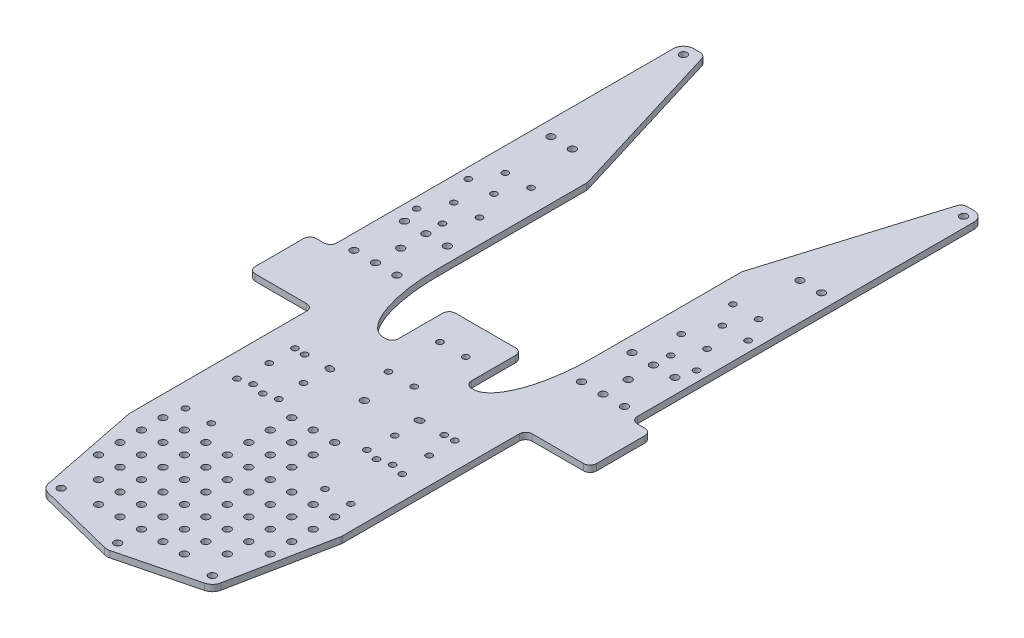
SolidWorks part; units mm, degrees
material "Acrylic (Medium-high impact)"
ref_plane "Front" through (0, 0, 0) normal (0, 0, 1) x (1, 0, 0)
ref_plane "Top" through (0, 0, 0) normal (0, 1, 0) x (1, 0, 0)
ref_plane "Right" through (0, 0, 0) normal (1, 0, 0) x (0, 0, -1)
sketch "Top Layout" plane through (0, 0, 0) normal (0, 1, 0) x (1, 0, 0)
  line L0 (45.5, 0) -> (0, 0) construction
  line L6 (15.5, -88.75) -> (58.5, -88.75) construction
  line L25 (45.5, 0) -> (88.5, 0) construction
  line L26 (88.5, 70) -> (88.5, -70) construction
  line L27 (58.5, -18.75) -> (58.5, -158.75) construction
  line L31 (36, 88.75) -> (79, 88.75) construction
  line L32 (79, 158.75) -> (79, 18.75) construction
  point P0 (0, 0)
  point P6 (0, 0)
  point P8 (53, -32.3497)
  line B0 (70, 100) -> (36, 100) construction
  line B1 (70, 100) -> (70, 53.5) construction
  line B2 (70, 53.5) -> (36, 53.5) construction
  line B3 (36, 100) -> (36, 53.5) construction
  line B4 (53, 100) -> (53, 88.75) construction
  line B5 (-6, -22.6978) -> (-6, 1.3022) construction
  line B6 (-17, -29.9478) -> (-17, 16.5522) construction
  line B7 (-17, -29.9478) -> (17, -29.9478) construction
  line B8 (17, -29.9478) -> (17, 16.5522) construction
  line B9 (-17, 16.5522) -> (17, 16.5522) construction
  line B10 (-6, 1.3022) -> (6, 1.3022) construction
  line B11 (6, 1.3022) -> (6, -22.6978) construction
  line B12 (6, -22.6978) -> (-6, -22.6978) construction
  line B13 (0, -22.6978) -> (0, -29.9478) construction
  line B14 (17, 5.3022) -> (-19, 5.3022) construction
  line B15 (49.5, -53.5) -> (15.5, -53.5) construction
  line B16 (49.5, -53.5) -> (49.5, -100) construction
  line B17 (49.5, -100) -> (15.5, -100) construction
  line B18 (15.5, -53.5) -> (15.5, -100) construction
  line B19 (32.5, -88.75) -> (32.5, -100) construction
  line B20 (45.5, 14.25) -> (79.5, 14.25) construction
  line B21 (45.5, 14.25) -> (45.5, -14.25) construction
  line B22 (45.5, -14.25) -> (79.5, -14.25) construction
  line B23 (79.5, 14.25) -> (79.5, -14.25) construction
  dimension "D1" = 30
  dimension "D2" = 70
  dimension "D3" = 9.5
  dimension "D4" = 4.5
  dimension "D5" = 100
  dimension "D7" = 9
  dimension "D8" = 140
  dimension "D9" = 100
sketch_block_instance "Flat 430 Block-1"
sketch_block "Flat 430 Block" parameters "D1"=46.5, "D2"=34, "D3"=11.25, "D4"=6.2771, "D5"=20.8671, "D6"=8.1058, "D7"=13.2568
sketch_block_instance "DYNAMIXEL 430 Side-1"
sketch_block "DYNAMIXEL 430 Side" parameters "D1"=34, "D2"=46.5, "D3"=12, "D4"=24, "D5"=11.25, "D6"=2, "D7"=4
sketch_block_instance "Block2-1"
sketch_block "Block2" parameters "D1"=12, "D2"=11, "D3"=4, "D4"=24, "D5"=13.103, "D6"=44.647, "D7"=34
sketch_block_instance "DYNAMIXEL 430 TopBot-1"
sketch_block "DYNAMIXEL 430 TopBot" parameters "D1"=28.5, "D2"=34, "D3"=20.267, "D4"=13.9544, "D5"=12.6443, "D6"=6.0635
sketch "Sketch4" plane through (0, 0, 0) normal (1, 0, 0) x (0, 0, -1)
  line L1 (-100, 0) -> (100, 0)
  line L5 (100, -3) -> (-100, -3)
  line L8 (100, -3) -> (100, 0)
  line L9 (-100, -3) -> (-100, 0)
  line L10 (158.75, 0) -> (18.75, 0) construction
  line B0 (-100, 14.25) -> (-88.75, 14.25) construction
  line B1 (-53.5, 0) -> (-100, 0) construction
  line B2 (-53.5, 0) -> (-53.5, 28.5) construction
  line B3 (-53.5, 28.5) -> (-100, 28.5) construction
  line B4 (-100, 0) -> (-100, 28.5) construction
  line B5 (100, 14.25) -> (88.75, 14.25) construction
  line B6 (53.5, 28.5) -> (100, 28.5) construction
  line B7 (53.5, 28.5) -> (53.5, 0) construction
  line B8 (53.5, 0) -> (100, 0) construction
  line B9 (100, 28.5) -> (100, 0) construction
  dimension "D2" = 3
sketch_block_instance "DYNAMIXEL 430 Front-1"
sketch_block "DYNAMIXEL 430 Front" parameters "D1"=46.5, "D2"=28.5, "D3"=11.25, "D4"=8, "D5"=8, "D6"=11, "D7"=11
sketch_block_instance "DYNAMIXEL 430 Front-3"
extrude "Boss-Extrude1" add sketch "Sketch4" along normal up to vertex (79.5 mm away)
ref_plane "Plane1" through (45.5, 0, 0) normal (1, 0, 0) x (0, 0, -1)
hole_wizard "M2.5 Clearance Hole2" positions "Sketch12" profile "Sketch13" hole size "M2.5" standard "ANSI Metric" end condition through all
sketch "Sketch12" plane through (0, -3, 0) normal (0, 1, 0) x (1, 0, 0)
  point P0 (26.5, -84.75)
  point P3 (38.5, -84.75)
  point P6 (38.5, -60.75)
  point P9 (26.5, -60.75)
  point P18 (59, 84.75)
  point P21 (47, 84.75)
  point P24 (47, 60.75)
  point P27 (59, 60.75)
  point P30 (6, -22.6978)
  point P32 (6, 1.3022)
  point P38 (65.2, 73.65)
  point P41 (53.2, 73.65)
  point P44 (53.2, 49.65)
  point P47 (65.2, 49.65)
sketch "Sketch13" plane through (26.5, -3, 84.75) normal (1, 0, 0) x (0, 0, -1)
  line L0 (0, 0) -> (0, 3)
  line L1 (0, 3) -> (1.45, 3)
  line L2 (1.45, 3) -> (1.45, 0)
  line L5 (1.45, 0) -> (0, 0)
  line L11 (0, -6.35) -> (0, 107.95) construction
  dimension "Thru Hole Dia." = 2.9
  dimension "Thru Hole Depth" = 3
sketch "Sketch14" plane through (0, 0, 0) normal (0, 1, 0) x (1, 0, 0)
  line L1 (79.5, 100) -> (70, 100)
  line L2 (79.5, 100) -> (79.5, 14.25)
  line L3 (79.5, 14.25) -> (70, 14.25)
  line L4 (70, 100) -> (70, 14.25)
  line L5 (45.5, -14.25) -> (79.5, -14.25) construction
  line L6 (79.5, -100) -> (49.5, -100)
  line L7 (79.5, -100) -> (79.5, -14.25)
  line L8 (79.5, -14.25) -> (49.5, -14.25)
  line L9 (49.5, -100) -> (49.5, -14.25)
  line L10 (17, 16.5522) -> (17, -10)
  line L11 (0, 100) -> (36, 100)
  line L12 (0, 100) -> (0, 16.5522)
  line L13 (0, 16.5522) -> (17, 16.5522)
  line L15 (17, -29.9478) -> (17, 16.5522) construction
  line L16 (17, -10) -> (36, -10)
  line L17 (36, -10) -> (36, 100)
  line L18 (79.5, 100) -> (0, 100) construction
  line L21 (36, 100) -> (36, 53.5) construction
  line L22 (45.5, 14.25) -> (79.5, 14.25) construction
  point P4 (49.5, -14.25)
  point P5 (70, 14.25)
  point P26 (0, 0)
  point P30 (0, 0)
  dimension "D2" = 110
extrude "Cut-Extrude1" cut sketch "Sketch14" against normal through all
fillet "Fillet3" radius 15 1 edges at (36, -1.5, 10)
mirror "Mirror1" about plane through (0, 0, 0) normal (1, 0, 0) of bodies 121
sketch "Sketch18" plane through (0, 0, 0) normal (0, 1, 0) x (1, 0, 0)
  line L0 (0, -50) -> (0, 50) construction
  line L2 (36.4427, -150.774) -> (1.2271, -159.6893)
  line L3 (-1.2271, -159.6893) -> (-36.4427, -150.774)
  line L4 (49.5, -100) -> (-49.5, -100) construction
  line L5 (49.5, -100) -> (40.1185, -146.9075)
  line L6 (-49.5, -100) -> (-40.1185, -146.9075)
  line L7 (49.5, -100) -> (-49.5, -100)
  line L8 (49.5, -100) -> (49.5, -135.5765) construction
  line L9 (-49.5, -100) -> (-49.5, -135.5765) construction
  line L10 (45.5, 0) -> (0, 0) construction
  line L11 (36, 30) -> (36, 100) construction
  line L12 (70, 100) -> (36, 100)
  line L13 (70, 100) -> (70, 173.9875)
  line L16 (70, 100) -> (36, 100) construction
  line L19 (-70, 100) -> (-70, 173.9875)
  line L20 (-70, 100) -> (-36, 100)
  line L21 (36, 100) -> (60, 178.75)
  line L22 (60, 178.75) -> (65.2375, 178.75)
  line L23 (-36, 100) -> (-60, 178.75)
  line L24 (-60, 178.75) -> (-65.2375, 178.75)
  arc A0 (-1.2271, -159.6893) -> (1.2271, -159.6893) centre (0, -154.8423) ccw
  arc A1 (-36.4427, -150.774) -> (-40.1185, -146.9075) centre (-35.2156, -145.9269) cw
  arc A2 (40.1185, -146.9075) -> (36.4427, -150.774) centre (35.2156, -145.9269) cw
  circle A3 centre (20.5, -35.25) radius 3.5 construction
  arc A4 (-70, 173.9875) -> (-65.2375, 178.75) centre (-65.2375, 173.9875) cw
  arc A5 (70, 173.9875) -> (65.2375, 178.75) centre (65.2375, 173.9875) ccw
  spline S0 degree 3 poles (49.5, -135.5765) (49.5, -157.7459) (43.8224, -199.0999) (14.2477, -213.5314) (0, -213.5314) knots 0 0 0 0 0.669072 1 1 1 1 construction
  spline S1 degree 3 poles (-49.5, -135.5765) (-49.5, -157.7459) (-43.8224, -199.0999) (-14.2477, -213.5314) (0, -213.5314) knots 0 0 0 0 0.669072 1 1 1 1 construction
  point P18 (0, -160)
  point P21 (-39.5, -150)
  point P25 (39.5, -150)
  point P42 (-70, 178.75)
  point P46 (70, 178.75)
  line B0 (20.5, -59.25) -> (20.5, -35.25) construction
  line B1 (9.5, -66.5) -> (9.5, -20) construction
  line B2 (9.5, -66.5) -> (43.5, -66.5) construction
  line B3 (43.5, -66.5) -> (43.5, -20) construction
  line B4 (9.5, -20) -> (43.5, -20) construction
  line B5 (20.5, -35.25) -> (32.5, -35.25) construction
  line B6 (32.5, -35.25) -> (32.5, -59.25) construction
  line B7 (32.5, -59.25) -> (20.5, -59.25) construction
  line B8 (26.5, -59.25) -> (26.5, -66.5) construction
  line B9 (43.5, -31.25) -> (7.5, -31.25) construction
  line B10 (-20.5, -59.25) -> (-20.5, -35.25) construction
  line B11 (-9.5, -66.5) -> (-9.5, -20) construction
  line B12 (-9.5, -66.5) -> (-43.5, -66.5) construction
  line B13 (-43.5, -66.5) -> (-43.5, -20) construction
  line B14 (-9.5, -20) -> (-43.5, -20) construction
  line B15 (-20.5, -35.25) -> (-32.5, -35.25) construction
  line B16 (-32.5, -35.25) -> (-32.5, -59.25) construction
  line B17 (-32.5, -59.25) -> (-20.5, -59.25) construction
  line B18 (-26.5, -59.25) -> (-26.5, -66.5) construction
  line B19 (-43.5, -31.25) -> (-7.5, -31.25) construction
  dimension "D4" = 5
  dimension "D6" = 5
  dimension "D8" = 7
  dimension "D11" = 4.7625
  dimension "D1" = 9.5
  dimension "D2" = 20
  dimension "D3" = 60
  dimension "D5" = 50
  dimension "D7" = 10
  dimension "D9" = 20
  dimension "D10" = 10
sketch_block_instance "DYNAMIXEL 430 Side-2"
sketch_block "Favorites" parameters "D1"=34, "D2"=46.5, "D3"=12, "D4"=24, "D5"=11.25, "D6"=2, "D7"=4
sketch_block_instance "DYNAMIXEL 430 Side-4"
extrude "Boss-Extrude2" add sketch "Sketch18" along direction (0, -1, 0) on the side against the normal up to surface (3 mm away)
hole_wizard "M3 Clearance Hole1" positions "Sketch15" profile "Sketch16" hole size "M3" standard "ANSI Metric" end condition through all
sketch "Sketch15" plane through (0, 0, 0) normal (0, 1, 0) x (1, 0, 0)
  line L9 (0, -50) -> (0, 50) construction
  line L10 (-17, -29.9478) -> (17, -29.9478) construction
  line L13 (53.2, 49.65) -> (38.5, -60.75) construction
  line L17 (36, 30) -> (70, 30) construction
  line L21 (70, 173.9875) -> (70, 14.25) construction
  line L23 (60, 178.75) -> (65.2375, 178.75) construction
  line L24 (70, 173.9875) -> (70, 14.25) construction
  circle A0 centre (65.2375, 173.9875) radius 4.7625 construction
  point P0 (0, -39.9478)
  point P2 (0, -154.8423)
  point P8 (53, 30)
  point P44 (-53, 30)
  point P74 (35.2156, -145.9269)
  point P93 (-35.2156, -145.9269)
  point P123 (65.2375, 173.9875)
  point P132 (-65.2375, 173.9875)
  dimension "D1" = 9.525
  dimension "D2" = 10
sketch "Sketch16" plane through (0, 0, 39.9478) normal (1, 0, 0) x (0, 0, 1)
  line L0 (0, 0) -> (0, 3.075)
  line L1 (0, 3.075) -> (1.7, 3.075)
  line L2 (1.7, 3.075) -> (1.7, 0)
  line L5 (1.7, 0) -> (0, 0)
  line L11 (0, -6.35) -> (0, 107.95) construction
  dimension "Thru Hole Dia." = 3.4
  dimension "Thru Hole Depth" = 3.075
fillet "Fillet2" radius 3 18 edges at (17, -1.5, 10) (17, -1.5, -16.5522) (-17, -1.5, -16.5522) (-17, -1.5, 10) (-70, -1.5, -14.25) (-79.5, -1.5, -14.25) (-79.5, -1.5, 14.25) (-49.5, -1.5, 14.25) (49.5, -1.5, 14.25) (79.5, -1.5, 14.25) (79.5, -1.5, -14.25) (70, -1.5, -14.25) (49.5, -1.5, 100) (-49.5, -1.5, 100) (-36, -1.5, -100) (-60, -1.5, -178.75) (60, -1.5, -178.75) (36, -1.5, -100)
hole_wizard "M2.5 Clearance Hole1" positions "Sketch19" profile "Sketch20" hole size "M2.5" standard "ANSI Metric" end condition through all
sketch "Sketch19" plane through (0, 0, 0) normal (0, 1, 0) x (1, 0, 0)
  line L0 (0, -50) -> (0, 50) construction
  point P0 (32.5, -59.25)
  point P3 (20.5, -59.25)
  point P6 (20.5, -35.25)
  point P9 (32.5, -35.25)
  point P12 (-20.5, -35.25)
  point P15 (-32.5, -35.25)
  point P18 (-32.5, -59.25)
  point P21 (-20.5, -59.25)
  point P24 (37.25, -47)
  point P27 (37.25, -35)
  point P30 (21.25, -35)
  point P33 (21.25, -47)
  point P40 (-21.25, -47)
  point P41 (-37.25, -47)
  point P42 (-37.25, -35)
  point P43 (-21.25, -35)
sketch "Sketch20" plane through (32.5, 0, 59.25) normal (1, 0, 0) x (0, 0, 1)
  line L0 (0, 0) -> (0, 3.075)
  line L1 (0, 3.075) -> (1.45, 3.075)
  line L2 (1.45, 3.075) -> (1.45, 0)
  line L5 (1.45, 0) -> (0, 0)
  line L11 (0, -6.35) -> (0, 107.95) construction
  dimension "Thru Hole Dia." = 2.9
  dimension "Thru Hole Depth" = 3.075
hole_wizard "M3 Clearance Hole2" positions "Sketch22" profile "Sketch23" hole size "M3" standard "ANSI Metric"
sketch "Sketch22" plane through (0, 0, 0) normal (0, 1, 0) x (1, 0, 0)
  line L1 (40, -93.75) -> (30, -93.75) construction
  line L2 (40, -93.75) -> (40, -103.75) construction
  line L3 (15.5, -88.75) -> (58.5, -88.75) construction
  line L4 (0, -50) -> (0, 50) construction
  line L5 (-40, -93.75) -> (-40, -103.75) construction
  line L6 (-40, -93.75) -> (-30, -93.75) construction
  line L7 (10, -93.75) -> (10, -83.75) construction
  line L9 (53, 53.5) -> (53, 30) construction
  line L10 (70, 53.5) -> (36, 53.5) construction
  line L12 (53, 41.75) -> (63, 41.75) construction
  line L14 (53, 41.75) -> (43, 41.75) construction
  line L16 (70, 100) -> (36, 100) construction
  line L17 (-53, 41.75) -> (-43, 41.75) construction
  line L18 (-53, 41.75) -> (-63, 41.75) construction
  line L19 (-53, 53.5) -> (-53, 30) construction
  line L20 (36, 30) -> (70, 30) construction
  line L21 (70, 173.9875) -> (70, 17.25) construction
  line L23 (-53, 18.25) -> (-63, 18.25) construction
  line L24 (-53, 18.25) -> (-43, 18.25) construction
  line L25 (53, 18.25) -> (43, 18.25) construction
  line L26 (53, 18.25) -> (63, 18.25) construction
  point P0 (40, -93.75)
  point P12 (30, -93.75)
  point P13 (20, -93.75)
  point P14 (10, -93.75)
  point P15 (0, -93.75)
  point P16 (30, -103.75)
  point P17 (20, -103.75)
  point P18 (10, -103.75)
  point P19 (0, -103.75)
  point P20 (30, -113.75)
  point P21 (20, -113.75)
  point P22 (10, -113.75)
  point P23 (0, -113.75)
  point P24 (30, -123.75)
  point P25 (20, -123.75)
  point P26 (10, -123.75)
  point P27 (0, -123.75)
  point P28 (30, -133.75)
  point P29 (20, -133.75)
  point P30 (10, -133.75)
  point P31 (0, -133.75)
  point P33 (20, -143.75)
  point P34 (10, -143.75)
  point P35 (0, -143.75)
  point P40 (40, -103.75)
  point P41 (40, -113.75)
  point P42 (40, -123.75)
  point P53 (40, -153.75) [skipped]
  point P54 (10, -153.75) [skipped]
  point P55 (20, -153.75) [skipped]
  point P56 (30, -153.75) [skipped]
  point P57 (40, -143.75) [skipped]
  point P58 (30, -143.75) [skipped]
  point P59 (40, -133.75) [skipped]
  point P66 (-40, -123.75)
  point P67 (-40, -113.75)
  point P68 (-40, -103.75)
  point P69 (-10, -143.75)
  point P70 (-20, -143.75)
  point P71 (-10, -133.75)
  point P72 (-20, -133.75)
  point P73 (-30, -133.75)
  point P74 (-10, -123.75)
  point P75 (-20, -123.75)
  point P76 (-30, -123.75)
  point P77 (-10, -113.75)
  point P78 (-20, -113.75)
  point P79 (-30, -113.75)
  point P80 (-10, -103.75)
  point P81 (-20, -103.75)
  point P82 (-30, -103.75)
  point P83 (-10, -93.75)
  point P84 (-20, -93.75)
  point P85 (-30, -93.75)
  point P86 (-40, -93.75)
  point P97 (10, -83.75)
  point P98 (0, -83.75)
  point P99 (-10, -83.75)
  point P100 (10, -73.75)
  point P101 (0, -73.75)
  point P102 (-10, -73.75)
  point P103 (10, -63.75)
  point P104 (0, -63.75)
  point P105 (-10, -63.75)
  point P114 (43, 41.75)
  point P116 (63, 41.75)
  point P118 (53, 110)
  point P120 (63, 110)
  point P150 (-63, 110)
  point P151 (-53, 110)
  point P152 (-63, 41.75)
  point P153 (-43, 41.75)
  point P166 (-43, 18.25)
  point P167 (-63, 18.25)
  point P168 (63, 18.25)
  point P169 (43, 18.25)
  point P172 (53, 18.25)
  point P175 (53, 41.75)
  point P178 (-53, 41.75)
  point P181 (-53, 18.25)
  point P182 (0, -153.75) [skipped]
  dimension "D1" = 5
  dimension "D3" = 10
  dimension "D4" = 10
  dimension "D5" = 5
  dimension "D7" = 10
  dimension "D8" = 10
  dimension "D9" = 10
  dimension "D10" = 10
  dimension "D2" = 7
  dimension "D6" = 4
sketch "Sketch23" plane through (40, 0, 93.75) normal (1, 0, 0) x (0, 0, 1)
  line L0 (0, 0) -> (0, 3.075)
  line L1 (0, 3.075) -> (1.7, 3.075)
  line L2 (1.7, 3.075) -> (1.7, 0)
  line L5 (1.7, 0) -> (0, 0)
  line L11 (0, -6.35) -> (0, 107.95) construction
  dimension "Thru Hole Dia." = 3.4
  dimension "Thru Hole Depth" = 3.075
fillet "Fillet4" radius 1 4 edges at (-20.4338, -1.5, 33.8015) (-21.3162, -1.5, 36.4485) (21.3162, -1.5, 36.4485) (20.4338, -1.5, 33.8015)
